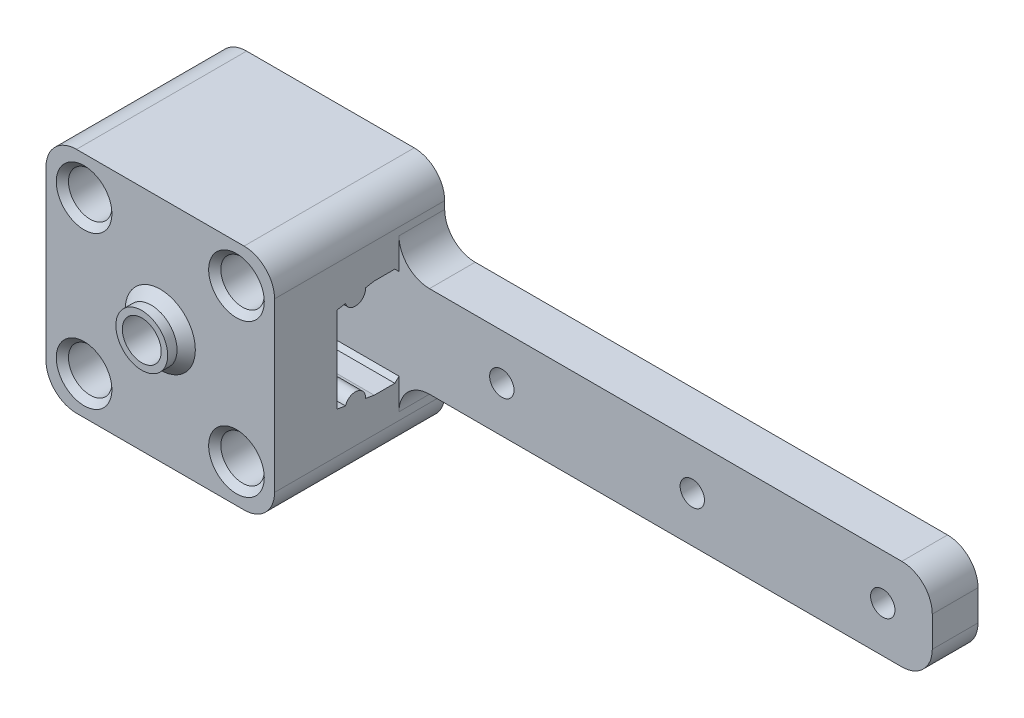
SolidWorks part; units mm, degrees
ref_plane "Front Plane" through (0, 0, 0) normal (0, 0, 1) x (1, 0, 0)
ref_plane "Top Plane" through (0, 0, 0) normal (0, 1, 0) x (1, 0, 0)
ref_plane "Right Plane" through (0, 0, 0) normal (1, 0, 0) x (0, 0, -1)
sketch "Sketch1" plane through (0, 0, 0) normal (0, 0, 1) x (1, 0, 0)
  line L0 (10, 20) -> (10, 0) construction
  line L1 (0, 0) -> (20, 0) construction
  line L2 (0, 0) -> (0, 20) construction
  line L3 (0, 20) -> (20, 20) construction
  line L4 (20, 0) -> (20, 20) construction
  line L5 (10, 10) -> (68.0208, 10) construction
  line L6 (-5, -5) -> (25, -5)
  line L7 (-5, -5) -> (-5, 25)
  line L8 (-5, 25) -> (25, 25)
  line L9 (25, -5) -> (25, 25)
  line L10 (-5, -5) -> (25, 25) construction
  line L11 (-5, 25) -> (25, -5) construction
  line L13 (25, 16) -> (95, 16)
  line L14 (25, 16) -> (25, 4)
  line L15 (25, 4) -> (95, 4)
  line L16 (95, 16) -> (95, 4)
  circle A0 centre (0, 0) radius 1.6
  circle A1 centre (0, 20) radius 1.6
  circle A2 centre (20, 20) radius 1.6
  circle A3 centre (20, 0) radius 1.6
  point P11 (10, 10)
  dimension "D2" = 3.2
  dimension "D1" = 20
  dimension "D3" = 30
  dimension "D4" = 30
  dimension "D5" = 12
  dimension "D6" = 6
  dimension "D7" = 70
extrude "Boss-Extrude1" add sketch "Sketch1" along normal blind 6 contours L6 L9 L8 L7 A3 A2 A1 A0 | L16 L13 L9 L15 region at (10, 10, 0) region at (60, 10, 0)
extrude "Boss-Extrude2" add sketch "Sketch1<3>" along normal blind 22.33 contours L6 L9 L8 L7 A3 A2 A1 A0 region at (10, 10, 0)
sketch "Sketch1<3>" plane through (0, 0, 0) normal (0, 0, 1) x (1, 0, 0) same geometry as "Sketch1"
sketch "Sketch2" plane through (25, 0, 0) normal (1, 0, 0) x (0, 0, -1)
  line L0 (-6.5408, 16.4886) -> (-9.2445, 16.4886)
  line L1 (-9.2445, 16.4886) -> (-10.3819, 16.2881)
  line L2 (-13.0245, 15.8221) -> (-14.1113, 15.6305)
  line L3 (-14.1113, 15.6305) -> (-14.1113, 4.3688)
  line L4 (-14.1113, 4.3688) -> (-13.0245, 4.1771)
  line L5 (-10.3819, 3.7112) -> (-9.2445, 3.5106)
  line L6 (-9.2445, 3.5106) -> (-6.5408, 3.5106)
  line L7 (-6.5408, 3.5106) -> (-6, 4.0514)
  line L9 (-6, 15.9479) -> (-6.5408, 16.4886)
  line L11 (-22.33, -5) -> (0, -5) construction
  line L12 (-22.33, -5) -> (-22.33, 25) construction
  line L13 (-6, 15.9479) -> (-6, 4.0514)
  arc A0 (-13.0245, 15.8221) -> (-10.3819, 16.2881) centre (-11.732, 16.2183) ccw
  arc A1 (-10.3819, 3.7112) -> (-13.0245, 4.1771) centre (-11.732, 3.781) ccw
extrude "Cut-Extrude1" cut sketch "Sketch2" against normal blind 22.5
sketch "Sketch3" plane through (0, 0, 22.33) normal (0, 0, 1) x (1, 0, 0)
  line L0 (-5, 10) -> (25, 10) construction
  line L1 (-5, -5) -> (-5, 25) construction
  line L2 (25, -5) -> (25, 25) construction
  line L3 (10, -5) -> (10, 25) construction
  line L4 (-5, -5) -> (25, -5) construction
  line L5 (-5, 25) -> (25, 25) construction
  circle A0 centre (10, 10) radius 2.55
  dimension "D1" = 5.1
extrude "Cut-Extrude2" cut sketch "Sketch3" against normal blind 8
sketch "Sketch5" plane through (0, 0, 14.1113) normal (0, 0, -1) x (-1, 0, 0)
  line L1 (-5.3235, 10) -> (-7.6617, 14.05)
  line L2 (-7.6617, 14.05) -> (-12.3383, 14.05)
  line L3 (-12.3383, 14.05) -> (-14.6765, 10)
  line L4 (-14.6765, 10) -> (-12.3383, 5.95)
  line L5 (-12.3383, 5.95) -> (-7.6617, 5.95)
  line L6 (-7.6617, 5.95) -> (-5.3235, 10)
  line L8 (-25, 15.6305) -> (-25, 4.3688)
  line L9 (-25, 4.3688) -> (-2.5, 4.3688)
  line L10 (-2.5, 4.3688) -> (-2.5, 15.6305)
  line L11 (-2.5, 15.6305) -> (-25, 15.6305)
  line L12 (-25, 15.6305) -> (-25, 4.3688)
  line L13 (-25, 4.3688) -> (-2.5, 4.3688)
  line L14 (-2.5, 4.3688) -> (-2.5, 15.6305)
  line L15 (-2.5, 15.6305) -> (-25, 15.6305)
  circle A0 centre (-10, 10) radius 4.05
  circle A1 centre (-10, 10) radius 4.05 construction
  dimension "D2" = 8.1
  dimension "D3" = 8.1
  dimension "D1" = 0
extrude "Cut-Extrude3" cut sketch "Sketch5" against normal blind 4.5 contours A0 | A0 L2 L3 | A0 L3 L4 | A0 L4 L5 | A0 L5 L6 | A0 L6 L1 | A0 L1 L2 region at (5.8141, 10, 14.1113) region at (7.907, 13.6251, 14.1113) region at (10, 10, 14.1113) region at (7.907, 6.3749, 14.1113) region at (12.093, 13.6251, 14.1113) region at (12.093, 6.3749, 14.1113) region at (14.1859, 10, 14.1113)
sketch "Sketch6" plane through (0, 0, 0) normal (0, 0, -1) x (-1, 0, 0)
  line L0 (-20, 0) -> (0, 20) construction
  line L1 (0, 20) -> (0, 0) construction
  line L2 (0, 0) -> (-20, 20) construction
  circle A0 centre (-10, 10) radius 5
  dimension "D1" = 10
extrude "Cut-Extrude5" cut sketch "Sketch6" against normal blind 8.6
sketch "Sketch7" plane through (0, 0, 0) normal (0, 0, -1) x (-1, 0, 0)
  line L1 (5, -5) -> (-3.5, -5)
  line L2 (5, -5) -> (5, 25)
  line L3 (5, 25) -> (-3.5, 25)
  line L4 (-3.5, -5) -> (-3.5, 25)
  line L5 (5, 25) -> (-25, 25) construction
  line L6 (-95, 10) -> (-3.5, 10) construction
  line L7 (-95, 16) -> (-95, 4) construction
  line L8 (-3.5, 10) -> (-3.5, 16)
  line L9 (-25, 4) -> (-95, 4) construction
  line L10 (-3.5, 16) -> (-65, 16)
  line L11 (-3.5, 16) -> (-3.5, 4)
  line L12 (-3.5, 4) -> (-65, 4)
  line L13 (-65, 16) -> (-65, 4)
  circle A0 centre (-38.5, 10) radius 1.6
  circle A1 centre (-63.5, 10) radius 1.6
  circle A2 centre (-88.5, 10) radius 1.6
  dimension "D4" = 35
  dimension "D5" = 60
  dimension "D6" = 3.2
  dimension "D7" = 3.2
  dimension "D1" = 30
  dimension "D2" = 8.5
  dimension "D3" = 6
  dimension "D8" = 25
extrude "Cut-Extrude6" cut sketch "Sketch7" against normal through all contours L6 A2 | A2 L6 | A1 | A0 region at (88.5, 9.3209, 0) region at (88.5, 10.6791, 0)
sketch "Sketch8" plane through (0, 0, 22.33) normal (0, 0, 1) x (1, 0, 0)
  circle A0 centre (20, 20) radius 2.85
  circle A1 centre (20, 0) radius 2.85
  circle A2 centre (0, 0) radius 2.85
  circle A3 centre (0, 20) radius 2.85
  dimension "D4" = 5.7
extrude "Cut-Extrude7" cut sketch "Sketch8" against normal blind 18
sketch "Sketch9" plane through (0, 0, 22.33) normal (0, 0, 1) x (1, 0, 0)
  circle A0 centre (10, 10) radius 2.55
  circle A1 centre (10, 10) radius 3.4
  dimension "D1" = 5.1
  dimension "D2" = 6.8
extrude "Boss-Extrude3" add sketch "Sketch9" along normal blind 2.43
chamfer "Chamfer1" distance 1.2 angle 45 1 edges at (13.4, 10, 22.33)
fillet "Fillet3" radius 4 8 edges at (25, 4, 3) (25, 16, 3) (25, 25, 11.165) (-5, 25, 11.165) (-5, -5, 11.165) (25, -5, 11.165) (95, 4, 3) (95, 16, 3)
chamfer "Chamfer2" distance 0.8 angle 45 4 edges at (22.85, 0, 22.33) (2.85, 0, 22.33) (2.85, 20, 22.33) (22.85, 20, 22.33)
sketch "Sketch10" plane through (0, 0, 0) normal (0, 0, -1) x (-1, 0, 0)
  line L1 (-85.2668, 10) -> (-86.8834, 12.8)
  line L2 (-86.8834, 12.8) -> (-90.1166, 12.8)
  line L3 (-90.1166, 12.8) -> (-91.7332, 10)
  line L4 (-91.7332, 10) -> (-90.1166, 7.2)
  line L5 (-90.1166, 7.2) -> (-86.8834, 7.2)
  line L6 (-86.8834, 7.2) -> (-85.2668, 10)
  circle A3 centre (-88.5, 10) radius 2.8 construction
  dimension "D1" = 5.6
extrude "Cut-Extrude8" cut sketch "Sketch10" against normal blind 3
chamfer "Chamfer3" distance 0.8 angle 45 6 edges at (86.0751, 8.6, 0) (88.5, 7.2, 0) (90.9249, 8.6, 0) (90.9249, 11.4, 0) (86.0751, 11.4, 0) (88.5, 12.8, 0)
pattern_linear "LPattern1" count 3 spacing 25 along (-1, 0, 0) of "Chamfer3", "Cut-Extrude8"
